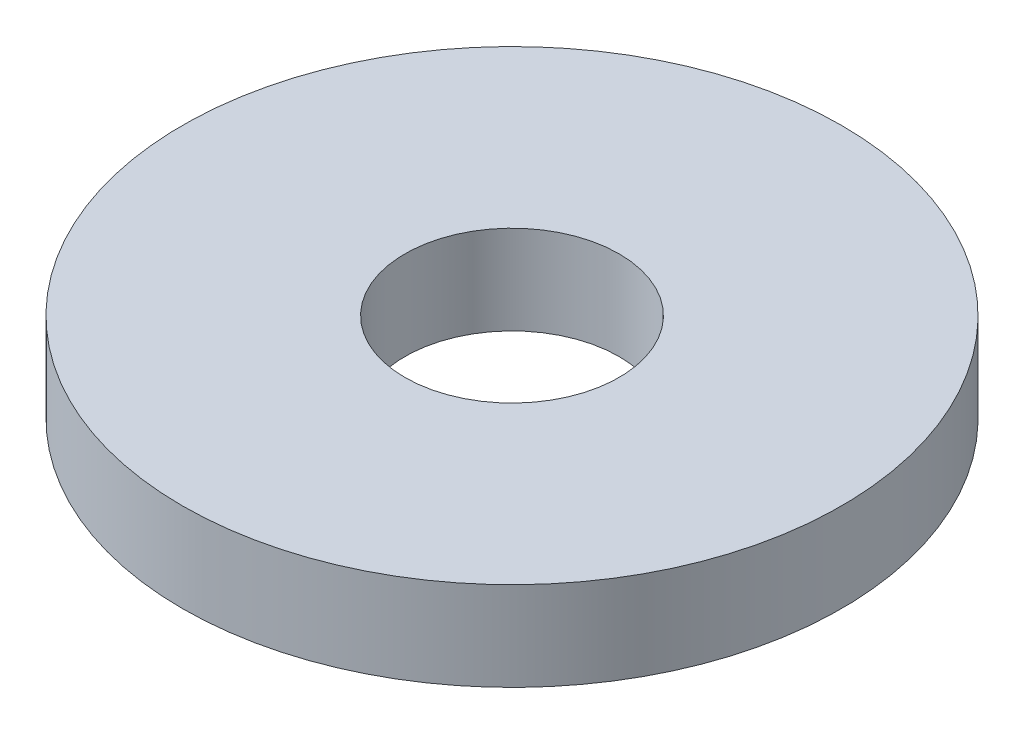
SolidWorks part; units mm, degrees
ref_plane "Front Plane" through (0, 0, 0) normal (0, 0, 1) x (1, 0, 0)
ref_plane "Top Plane" through (0, 0, 0) normal (0, 1, 0) x (1, 0, 0)
ref_plane "Right Plane" through (0, 0, 0) normal (1, 0, 0) x (0, 0, -1)
sketch "Sketch1" plane through (0, 0, 0) normal (0, 1, 0) x (1, 0, 0)
  circle A0 centre (0, 0) radius 100
  dimension "FLANGE_OD" = 200
extrude "Boss-Extrude1" add sketch "Sketch1" along normal blind 27
sketch "Sketch2" plane through (0, 0, 0) normal (0, 1, 0) x (1, 0, 0)
  circle A0 centre (0, 0) radius 32.5
  dimension "BORE_D" = 65
extrude "Cut-Extrude1" cut sketch "Sketch2" along normal through all
sketch "Sketch3" plane through (0, 27, 0) normal (0, 1, 0) x (1, 0, 0)
  circle A0 centre (0, 0) radius 20.8824 construction
  circle A1 centre (-20.8824, 0) radius 6.1946
  dimension "BOLT_D" = 12.3892
  dimension "BOLT_PCD" = 41.7648
extrude "Cut-Extrude2" cut sketch "Sketch3" against normal blind 24.7681 rebuild error yes
pattern_circular "CirPattern1" count 4 over 360 rebuild error yes
